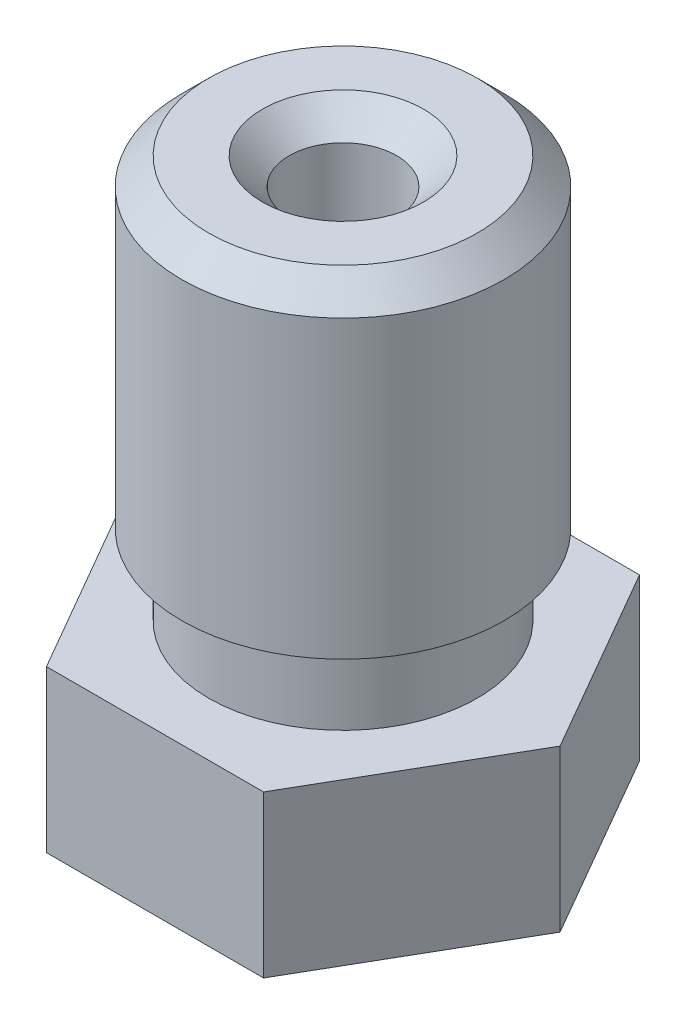
SolidWorks part; units mm, degrees
material "Brass"
ref_plane "Front Plane" through (0, 0, 0) normal (0, 0, 1) x (1, 0, 0)
ref_plane "Top Plane" through (0, 0, 0) normal (0, 1, 0) x (1, 0, 0)
ref_plane "Right Plane" through (0, 0, 0) normal (1, 0, 0) x (0, 0, -1)
ref_plane "Plane1" through (0, 0, 0) normal (0, -1, 0) x (1, 0, 0)
sketch "Sketch1" plane through (0, 0, 0) normal (0, -1, 0) x (1, 0, 0)
  line L0 (-2.0207, 3.5) -> (-4.0415, 0)
  line L1 (-4.0415, 0) -> (-2.0207, -3.5)
  line L2 (-2.0207, -3.5) -> (2.0207, -3.5)
  line L3 (2.0207, -3.5) -> (4.0415, 0)
  line L4 (4.0415, 0) -> (2.0207, 3.5)
  line L5 (2.0207, 3.5) -> (-2.0207, 3.5)
extrude "Boss-Extrude1" add sketch "Sketch1" against normal blind 3
ref_plane "Plane2" through (0, 0, 0) normal (0, 0, -1) x (-1, 0, 0)
sketch "Sketch2" plane through (0, 0, 0) normal (0, 0, -1) x (-1, 0, 0)
  line L0 (-2.5, 3) -> (0, 3)
  line L1 (0, 3) -> (0, 10.5)
  line L2 (0, 10.5) -> (-3, 10.5)
  line L3 (-3, 10.5) -> (-3, 4.5)
  line L4 (-3, 4.5) -> (-2.5, 4.5)
  line L5 (-2.5, 4.5) -> (-2.5, 3)
  line L6 (0, 3) -> (0, 10.5) construction
revolve "Revolve1" add sketch "Sketch2" angle 360 about L6 reverse direction yes
sketch "Sketch3" plane through (0, 0, 0) normal (0, 0, 1) x (1, 0, 0)
  line L0 (2.5, 0) -> (0, 0)
  line L1 (0, 0) -> (0, -2)
  line L2 (0, -2) -> (0.5, -2)
  line L3 (0.5, -2) -> (2.5, 0)
  line L4 (0, 0) -> (0, -2) construction
revolve "Revolve2" add sketch "Sketch3" angle 360 about L4 reverse direction yes
sketch "Sketch4" plane through (0, 0, 0) normal (0, 0, -1) x (-1, 0, 0)
  line L0 (-0.2, -2) -> (0, -2)
  line L1 (0, -2) -> (0, 10.5)
  line L2 (0, 10.5) -> (-1, 10.5)
  line L3 (-1, 10.5) -> (-1, 0)
  line L4 (-1, 0) -> (-0.75, -0.2273)
  line L5 (-0.75, -0.2273) -> (-0.75, -0.7)
  line L6 (-0.75, -0.7) -> (-0.2, -1.2)
  line L7 (-0.2, -1.2) -> (-0.2, -2)
  line L8 (0, -2) -> (0, 10.5) construction
revolve "Cut-Revolve1" cut sketch "Sketch4" angle 360 about L8 reverse direction yes
chamfer "Chamfer1" distance 0.5 angle 45 2 edges at (0, 10.5, 3) (0, 10.5, 1)
